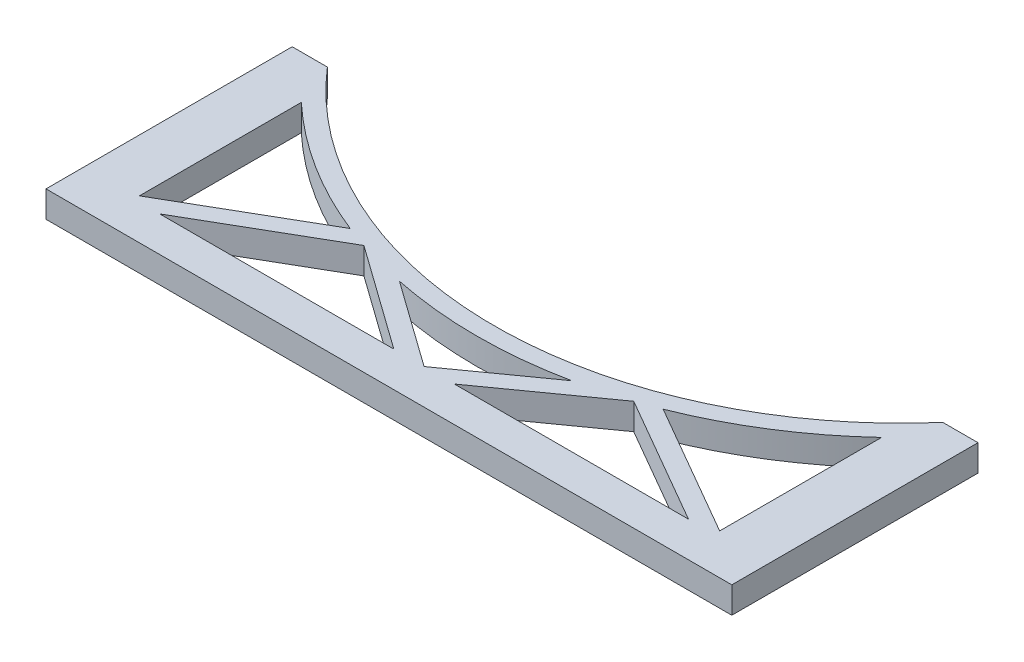
SolidWorks part; units mm, degrees
ref_plane "Front Plane" through (0, 0, 0) normal (0, 0, 1) x (1, 0, 0)
ref_plane "Top Plane" through (0, 0, 0) normal (0, 1, 0) x (1, 0, 0)
ref_plane "Right Plane" through (0, 0, 0) normal (1, 0, 0) x (0, 0, -1)
sketch "Sketch1" plane through (0, 0, 0) normal (0, 1, 0) x (1, 0, 0)
  line L0 (-123.825, 88.9) -> (-111.125, 88.9)
  line L1 (-123.825, 0) -> (123.825, 0)
  line L2 (-123.825, 0) -> (-123.825, 88.9)
  line L4 (123.825, 0) -> (123.825, 88.9)
  line L5 (123.825, 88.9) -> (111.125, 88.9)
  arc A1 (-111.125, 88.9) -> (111.125, 88.9) centre (0, 185.043) ccw
  point P4 (0, 0)
  point P9 (0, 38.1)
  dimension "D3" = 247.65
  dimension "D4" = 38.1
  dimension "D1" = 12.7
  dimension "D2" = 88.9
extrude "Boss-Extrude1" add sketch "Sketch1" along normal blind 9.525
sketch "Sketch2" plane through (0, 9.525, 0) normal (0, 1, 0) x (1, 0, 0)
  line L0 (-104.775, 73.146) -> (-104.775, 14.6647)
  line L1 (-104.775, 14.6647) -> (-56.494, 42.5398)
  line L2 (-95.478, 12.7) -> (-10.9243, 12.7)
  line L3 (-95.478, 12.7) -> (-48.7173, 39.6973)
  line L4 (-123.825, 0) -> (-97.0655, 15.4496) construction
  line L5 (-98.653, 18.1993) -> (-95.478, 12.7) construction
  line L6 (0, 12.7) -> (-31.1428, 34.9468)
  line L7 (0, 31.75) -> (0, 12.7)
  line L8 (-48.7173, 39.6973) -> (-10.9243, 12.7)
  line L9 (-123.825, 88.9) -> (-123.825, 0) construction
  line L10 (-123.825, 0) -> (123.825, 0) construction
  arc A0 (-111.125, 88.9) -> (111.125, 88.9) centre (0, 185.043) ccw construction
  arc A1 (-104.775, 73.146) -> (-56.494, 42.5398) centre (0, 185.043) ccw
  arc A2 (-31.1428, 34.9468) -> (0, 31.75) centre (0, 185.043) ccw
  point P2 (-122.9384, -13.5118)
  point P12 (-97.0655, 15.4496)
  point P20 (0, 0)
  point P21 (-104.775, 66.5865)
  point P25 (-123.825, 0)
  point P27 (-48.7173, 39.6973)
  point P28 (-15.2558, 12.7)
  dimension "D5" = 6.35
  dimension "D1" = 6.35
  dimension "D2" = 19.05
  dimension "D3" = 6.35
  dimension "D4" = 12.7
  dimension "D6" = 30
extrude "Cut-Extrude1" cut sketch "Sketch2" against normal through all
mirror "Mirror1" about plane through (0, 0, 0) normal (1, 0, 0) of "Cut-Extrude1"
